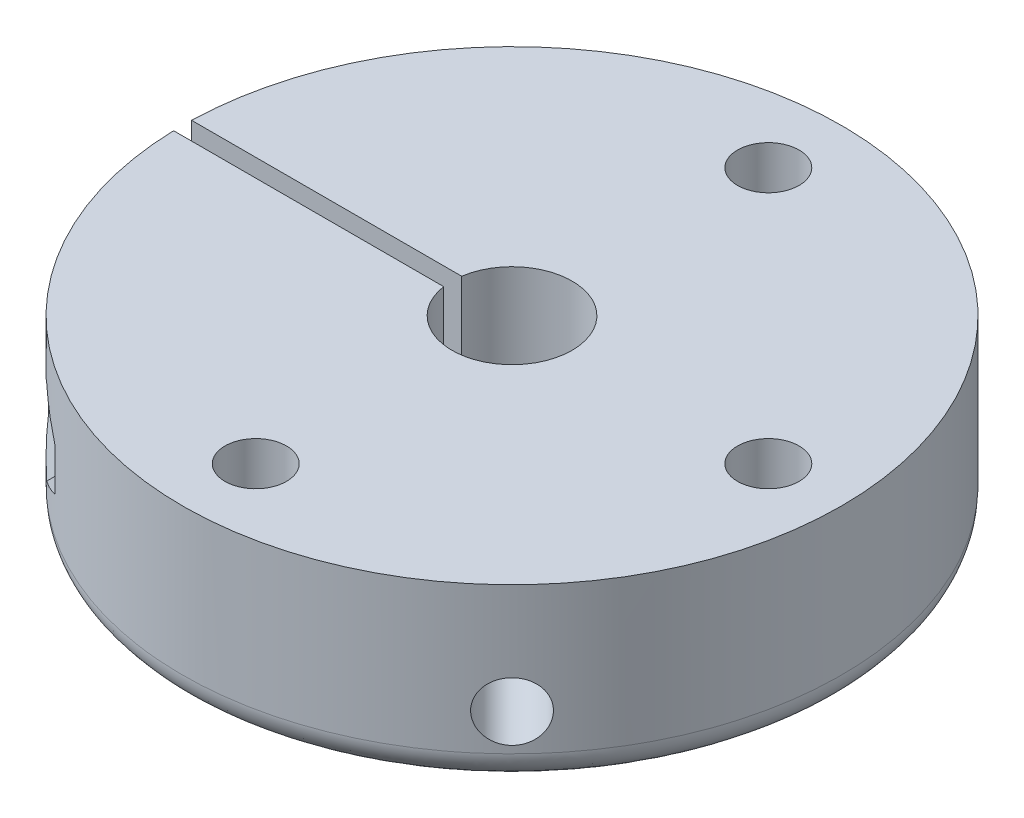
SolidWorks part; units mm, degrees
ref_plane "Front Plane" through (0, 0, 0) normal (0, 0, 1) x (1, 0, 0)
ref_plane "Top Plane" through (0, 0, 0) normal (0, 1, 0) x (1, 0, 0)
ref_plane "Right Plane" through (0, 0, 0) normal (1, 0, 0) x (0, 0, -1)
sketch "Sketch1" plane through (0, 0, 0) normal (0, 1, 0) x (1, 0, 0)
  line L1 (-22.4916, -0.615) -> (-4.0536, -0.615)
  line L3 (-22.4916, 0.615) -> (-4.0536, 0.615)
  line L5 (-22.4982, -0.2867) -> (-4.0623, 0.555) construction
  line L6 (-22.4982, 0.2867) -> (-4.0623, -0.555) construction
  circle A0 centre (0, 0) radius 4.1
  circle A1 centre (0, 0) radius 22.5
  circle A2 centre (0, 0) radius 17.5
  circle A3 centre (0, -17.5) radius 2.1
  circle A5 centre (0, 17.5) radius 2.1
  circle A6 centre (17.5, 0) radius 2.1
  arc A8 (-19.5993, 0.053) -> (-19.5993, -0.053) centre (-17.5, 0) ccw [skipped]
  point P16 (0, 0)
  dimension "D1" = 45
  dimension "D2" = 8.2
  dimension "D3" = 4.2
  dimension "D4" = 35
  dimension "D5" = 4
extrude "Boss-Extrude1" add sketch "Sketch1" along normal blind 12 contours A1 A6 A2 A3 A5 | A6 A2 A5 A3 A0 region at (-19.9904, 0, 1.2513) region at (-10.7714, 0, 1.1072)
ref_plane "Plane1" through (15.9099, 0, 15.9099) normal (0.7071, 0, 0.7071) x (0, -1, 0)
sketch "Sketch2" plane through (15.9099, 0, 15.9099) normal (0.7071, 0, 0.7071) x (0, -1, 0)
  line L0 (-12, 22.5) -> (-12, -22.5) construction
  circle A0 centre (-4.5, 0) radius 2
  dimension "D1" = 4
  dimension "D2" = 7.5
extrude "Cut-Extrude1" cut sketch "Sketch2" against normal up to next
ref_plane "Plane2" through (0, 0, -0.615) normal (0, 0, 1) x (1, 0, 0)
sketch "Sketch3" plane through (0, 0, -0.615) normal (0, 0, 1) x (1, 0, 0)
  line L0 (-22.4916, 12) -> (-22.4916, 0) construction
  circle A0 centre (-14.9916, 6) radius 3
  circle A1 centre (-14.9916, 6) radius 1.5
  dimension "D2" = 6
  dimension "D3" = 3
  dimension "D1" = 7.5
extrude "Cut-Extrude2" cut sketch "Sketch3" against normal up to surface (12.4232 mm away) from offset 6 contours A0 up to face at (14.4724, 4.0489, 17.2279) offset against normal yes
extrude "Cut-Extrude3" cut sketch "Sketch3<4>" against normal through all both and the other way through all contours A1 region at (-14.9916, 6, -0.615)
sketch "Sketch3<4>" plane through (0, 0, -0.615) normal (0, 0, 1) x (1, 0, 0) same geometry as "Sketch3"
sketch "Sketch5" plane through (0, 0, -0.615) normal (0, 0, 1) x (1, 0, 0)
  line L0 (-22.4916, 12) -> (-22.4916, 0) construction
  line L1 (-12.4916, 7.4434) -> (-14.9916, 8.8868)
  line L2 (-14.9916, 8.8868) -> (-17.4916, 7.4434)
  line L3 (-17.4916, 7.4434) -> (-17.4916, 4.5566)
  line L4 (-17.4916, 4.5566) -> (-14.9916, 3.1132)
  line L5 (-14.9916, 3.1132) -> (-12.4916, 4.5566)
  line L6 (-12.4916, 4.5566) -> (-12.4916, 7.4434)
  circle A0 centre (-14.9916, 6) radius 2.5 construction
  dimension "D1" = 5
  dimension "D2" = 0
extrude "Cut-Extrude4" cut sketch "Sketch5" along normal up to next from offset 11
fillet "Fillet1" radius 2 1 edges at (22.5, 0, 0) first distance on face at (17.5, 0, 2.1)
